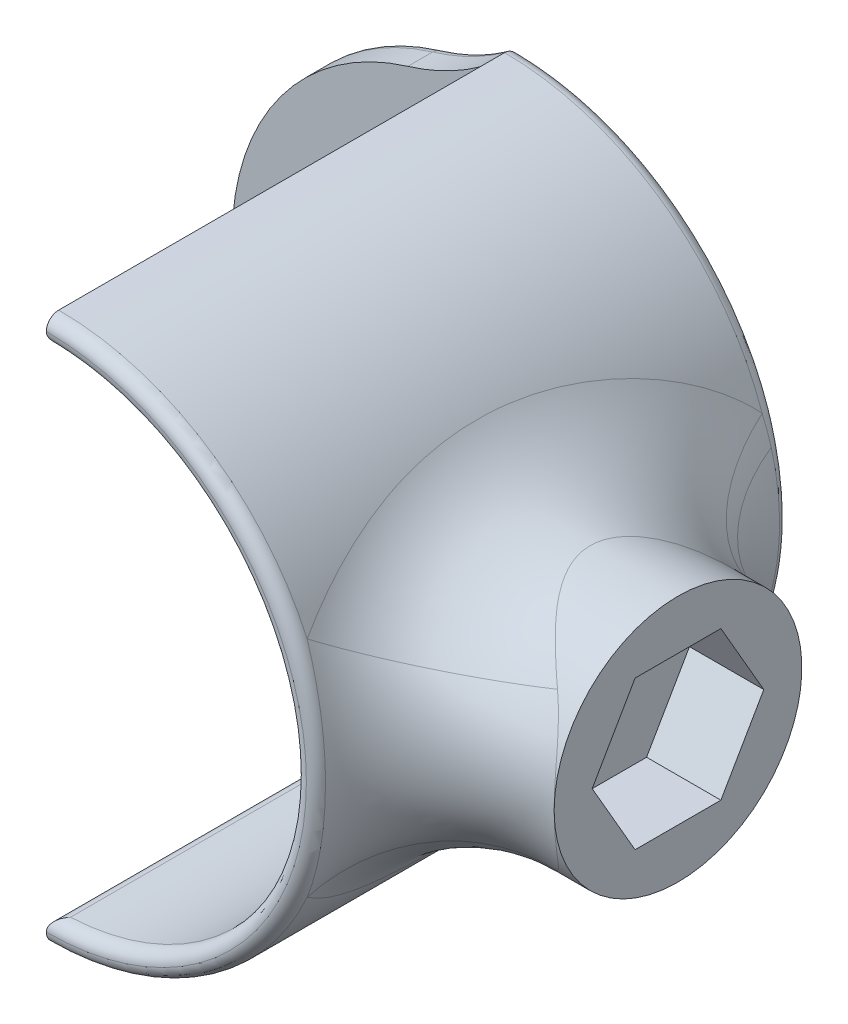
SolidWorks part; units mm, degrees
material "ABS"
ref_plane "Front Plane" through (0, 0, 0) normal (0, 0, 1) x (1, 0, 0)
ref_plane "Top Plane" through (0, 0, 0) normal (0, 1, 0) x (1, 0, 0)
ref_plane "Right Plane" through (0, 0, 0) normal (1, 0, 0) x (0, 0, -1)
sketch "Sketch1" plane through (0, 0, 0) normal (0, 0, 1) x (1, 0, 0)
  line L0 (0, 22) -> (0, 20)
  line L1 (0, -20) -> (0, -22)
  circle A0 centre (0, 0) radius 22
  circle A1 centre (0, 0) radius 15 construction
  circle A2 centre (0, 0) radius 20
  circle A6 centre (-15, 0) radius 1.5
  circle A7 centre (7.5, 12.9904) radius 1.5
  circle A8 centre (7.5, -12.9904) radius 1.5
  circle A9 centre (0, 0) radius 10
  point P18 (0, 0)
  dimension "D1" = 44
  dimension "D2" = 40
  dimension "D3" = 30
  dimension "D4" = 3
  dimension "D5" = 20
extrude "Boss-Extrude1" add sketch "Sketch1" along normal blind 3 contours A2 | A2 L1 A0 L0 region at (15.2085, 15.2085, 0) region at (13.7421, 13.7421, 0)
extrude "Boss-Extrude2" add sketch "Sketch1<3>" along normal blind 38 contours A2 L1 A0 L0 region at (15.2085, 15.2085, 0)
sketch "Sketch1<3>" plane through (0, 0, 0) normal (0, 0, 1) x (1, 0, 0) same geometry as "Sketch1"
fillet "Fillet3" radius 20 2 edges at (0, 20, 1.5) (0, -20, 1.5)
fillet "Fillet4" radius 1 8 edges at (-2.7901, 20.3311, 0) (-2.7901, -20.3311, 0) (-20, 0, 0) (22, 0, 0) (22, 0, 38) (20, 0, 38) (0, -20, 20.5) (0, 20, 20.5)
ref_plane "Plane1" through (22, 0, 0) normal (1, 0, 0) x (0, 0, -1)
sketch "Sketch2" plane through (22, 0, 0) normal (1, 0, 0) x (0, 0, -1)
  line L0 (0, -20.9977) -> (0, 20.9977) construction
  circle A0 centre (-20, 0) radius 10
  dimension "D1" = 20
  dimension "D2" = 20
extrude "Boss-Extrude3" add sketch "Sketch2" against normal up to surface up to face at (7.3333, 0, 13.6667)
extrude "Boss-Extrude8" add sketch "Sketch2<4>" along normal blind 5 contours A0
sketch "Sketch2<4>" plane through (22, 0, 0) normal (1, 0, 0) x (0, 0, -1) same geometry as "Sketch2"
sketch "Sketch12" plane through (27, 0, 0) normal (1, 0, 0) x (0, 0, -1)
  circle A0 centre (-20, 0) radius 1.5
  dimension "D1" = 3
extrude "Cut-Extrude10" cut sketch "Sketch12" against normal through all
sketch "Sketch13" plane through (27, 0, 0) normal (1, 0, 0) x (0, 0, -1)
  circle A0 centre (-20, 0) radius 2.5
  dimension "D1" = 5
extrude "Cut-Extrude11" cut sketch "Sketch13" along normal blind 3 and the other way through all from offset 6.9 offset against normal yes
sketch "Sketch14" plane through (27, 0, 0) normal (1, 0, 0) x (0, 0, -1)
  line L0 (-13.0718, 0) -> (-10, 0) construction
  line L1 (-13.0718, 0) -> (-16.5359, 6)
  line L2 (-16.5359, 6) -> (-23.4641, 6)
  line L3 (-23.4641, 6) -> (-26.9282, 0)
  line L4 (-26.9282, 0) -> (-23.4641, -6)
  line L5 (-23.4641, -6) -> (-16.5359, -6)
  line L6 (-16.5359, -6) -> (-13.0718, 0)
  circle A0 centre (-20, 0) radius 6 construction
  circle A1 centre (-20, 0) radius 10
  circle A2 centre (-20, 0) radius 10
  dimension "D2" = 12
  dimension "D1" = 0
extrude "Boss-Extrude10" add sketch "Sketch14" along normal blind 6
fillet "Fillet5" radius 12 1 edges at (21.9662, -1.2189, 29.9254)
